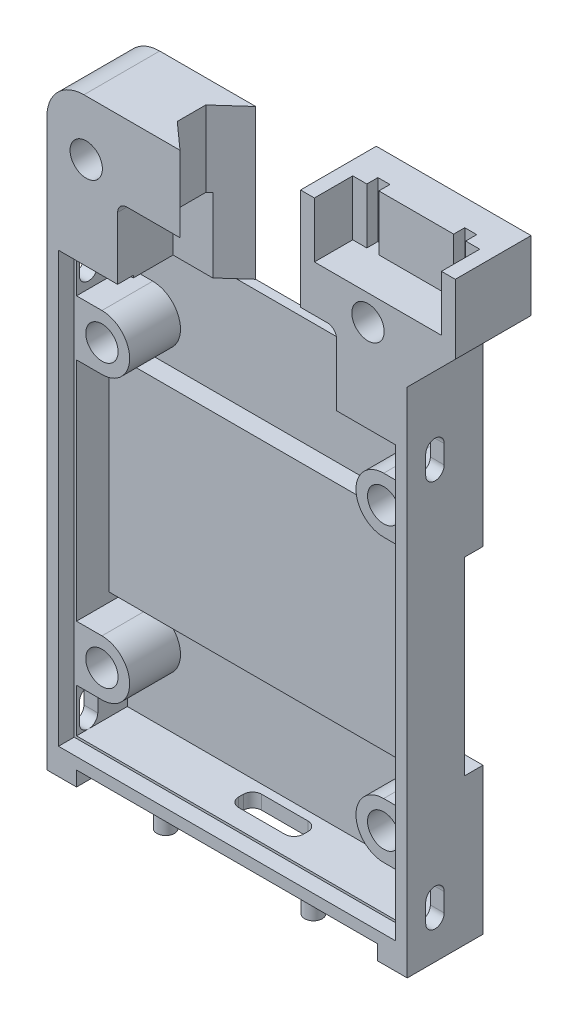
SolidWorks part; units mm, degrees
ref_plane "Front Plane" through (0, 0, 0) normal (0, 0, 1) x (1, 0, 0)
ref_plane "Top Plane" through (0, 0, 0) normal (0, 1, 0) x (1, 0, 0)
ref_plane "Right Plane" through (0, 0, 0) normal (1, 0, 0) x (0, 0, -1)
sketch "Sketch1" plane through (0, 0, 0) normal (0, 0, 1) x (1, 0, 0)
  line L0 (15.25, -20.35) -> (18, -20.35)
  line L1 (-19.5, -32.6) -> (19.5, -32.6)
  line L2 (-19.5, -32.6) -> (-19.5, 31.1)
  line L3 (-19.5, 31.1) -> (19.5, 31.1)
  line L4 (19.5, -32.6) -> (19.5, 31.1)
  line L5 (-15.25, -20.35) -> (-18, -20.35)
  line L6 (15.25, -26.35) -> (18, -26.35)
  line L7 (6.95, 31.1) -> (-15.5, 31.1) construction
  line L8 (-18, -31.1) -> (-18, 29.6)
  line L9 (-18, 29.6) -> (18, 29.6)
  line L10 (18, -31.1) -> (18, 29.6)
  line L11 (-18, -31.1) -> (18, -31.1)
  line L12 (-18, 14.9) -> (18, 14.9)
  line L13 (7.85, 14.9) -> (-4.95, 14.9) construction
  line L14 (-15.25, 4.15) -> (-18, 4.15)
  line L15 (-15.25, 10.15) -> (-18, 10.15)
  line L16 (15.25, 10.15) -> (18, 10.15)
  line L17 (15.25, 4.15) -> (18, 4.15)
  line L18 (-15.25, -26.35) -> (-18, -26.35)
  line L19 (19.5, -34.2) -> (19.5, -18.35) construction
  line L20 (-19.5, -34.2) -> (-19.5, -18.35) construction
  line L21 (15.3, -32.6) -> (-15.3, -32.6) construction
  line L22 (0, 31.1) -> (0, -32.6) construction
  line L23 (9.45, 26.9) -> (24.7, 26.9)
  line L24 (9.45, 26.9) -> (9.45, 33.9)
  line L25 (9.45, 33.9) -> (24.7, 33.9)
  line L26 (24.7, 26.9) -> (24.7, 33.9)
  line L27 (18, 29.6) -> (19.5, 31.1) construction
  line L28 (18.75, 30.35) -> (0, 30.35) construction
  line L29 (9.45, 26.9) -> (7.95, 26.9) construction
  line L30 (-7.95, 31.1) -> (7.95, 31.1)
  line L31 (-7.95, 31.1) -> (-7.95, 29.6)
  line L32 (-7.95, 29.6) -> (7.95, 29.6)
  line L33 (7.95, 31.1) -> (7.95, 29.6)
  line L34 (-7.95, 31.1) -> (7.95, 29.6) construction
  line L35 (-7.95, 29.6) -> (7.95, 31.1) construction
  line L36 (7.95, 26.9) -> (7.95, 29.6) construction
  line L37 (18, 29.6) -> (19.5, 29.6) construction
  line L38 (24.7, 26.4) -> (19.5, 21.2)
  line L39 (9.45, 33.9) -> (7.95, 33.9)
  line L40 (23.2, 33.9) -> (23.2, 26.9)
  line L41 (7.95, 33.9) -> (7.95, 31.1)
  line L42 (24.7, 30.4) -> (23.2, 30.4) construction
  line L43 (24.7, 26.9) -> (19.5, 26.9)
  line L44 (24.7, 26.9) -> (24.7, 26.4)
  line L45 (24.7, 26.4) -> (19.5, 26.4)
  line L46 (19.5, 26.9) -> (19.5, 26.4)
  circle A0 centre (15.25, -23.35) radius 1.75
  arc A1 (-15.5, 31.1) -> (-19.5, 27.1) centre (-15.5, 27.1) ccw construction
  circle A2 centre (15.25, -23.35) radius 3
  arc A3 (-15.5, 31.1) -> (-19.5, 27.1) centre (-15.5, 27.1) ccw
  arc A4 (-15.5, 29.6) -> (-18, 27.1) centre (-15.5, 27.1) ccw
  circle A6 centre (-15.25, -23.35) radius 1.75
  circle A7 centre (-15.25, -23.35) radius 1.75
  circle A8 centre (-15.25, 7.15) radius 1.75
  circle A9 centre (15.25, 7.15) radius 1.75
  circle A10 centre (15.25, 25.15) radius 1.75
  circle A11 centre (-15.25, 25.15) radius 1.75
  circle A12 centre (-15.25, -23.35) radius 3
  circle A13 centre (-15.25, -23.35) radius 3
  circle A14 centre (15.25, 7.15) radius 3
  circle A15 centre (-15.25, 7.15) radius 3
  dimension "D2" = 1.5
  dimension "D4" = 6
  dimension "D3" = 3.5
  dimension "D5" = 13.75
  dimension "D6" = 15.9
  dimension "D7" = 7
  dimension "D8" = 45
  dimension "D9" = 0.5
  dimension "D1" = 1.5
extrude "Base shape" add sketch "Sketch1" along normal up to surface (8.2 mm away) contours A15 L8 L9 L31 L3 A3 L2 L1 L4 L23 L10 A14 A2 L11 A12 | A12 L8 L18 | A12 L8 A6 | L8 A12 | A12 L5 L8 | A15 L8 L14 | A15 L8 A8 | L8 A15 | A15 L15 L8 | L23 A10 L24 L9 A4 L8 L12 L10 A11 | A4 L9 L8 | L33 L3 L31 L9 | L3 L33 L9 L24 | L24 L9 L10 L23 L4 L3 | L24 L23 L10 L9 | A14 L10 L16 | L10 A14 A9 | A14 L17 L10 | L10 A14 | L10 A2 L6 | A2 L10 A0 | L0 A2 L10 | A2 L10 | L40 L25 L24 L3 L4 L23 | L25 L40 L23 L26 | L38 L45 L4 | L45 L44 L23 L4 | L39 L41 L3 L24 region at (16.8481, -20.9099, 0) region at (17.3601, -20.8437, 0) region at (18.7469, -8.1, 0) region at (17.3601, -25.8563, 0) region at (18.1004, -23.35, 0) region at (17.3601, 4.6437, 0) region at (16.8481, 4.7099, 0) region at (18.1004, 7.15, 0) region at (17.3601, 9.6563, 0) region at (-17.3601, -25.8563, 0) region at (-0.6044, 21.831, 0) region at (-18.1004, -23.35, 0) region at (-17.9169, -23.35, 0) region at (13.725, 28.25, 0) region at (15.3803, 29.9053, 0) region at (-17.3601, -20.8437, 0) region at (22.1, 26.65, 0) region at (17.77, 31.4935, 0) region at (-17.3601, 9.6563, 0) region at (-17.4416, 29.0416, 0) region at (8.7, 30.35, 0) region at (21.2333, 24.6667, 0) region at (23.95, 30.4, 0) region at (-16.8481, 9.5901, 0) region at (-18.1004, 7.15, 0) region at (-17.3601, 4.6437, 0) region at (0, 30.35, 0) region at (8.7, 32.5, 0)
sketch "Sketch3" plane through (19.5, 0, 0) normal (1, 0, 0) x (0, 0, -1)
  line L1 (0, -18.35) -> (-2, -18.35)
  line L2 (0, -18.35) -> (0, 2.15)
  line L3 (0, 2.15) -> (-2, 2.15)
  line L4 (-2, -18.35) -> (-2, 2.15)
  line L5 (0, -18.35) -> (2, -18.35) construction
  line L6 (0, 2.15) -> (2, 2.15) construction
  line L7 (0, -32.6) -> (0, 21.2) construction
  dimension "D1" = 2
extrude "Strap cut" cut sketch "Sketch3" against normal through all
sketch "Sketch4" plane through (0, 31.1, 0) normal (0, 1, 0) x (1, 0, 0)
  line L2 (7.95, 0) -> (-5.0998, 0)
  line L4 (-15.5, 0) -> (7.95, 0) construction
  line L5 (-15.5, -8.2) -> (7.95, -8.2) construction
  line L6 (7.95, -8.2) -> (-5.0998, -8.2)
  line L12 (7.95, -8.3) -> (7.95, 0.1)
  line L13 (7.95, 0.1) -> (-4.9883, 0.1)
  line L14 (-4.9883, 0.1) -> (-7.95, -2.5553)
  line L15 (-7.95, -2.5553) -> (-7.95, -5.6447)
  line L16 (-7.95, -5.6447) -> (-4.9883, -8.3)
  line L17 (-4.9883, -8.3) -> (7.95, -8.3)
  line L18 (7.95, -8.3) -> (7.95, 0.1)
  line L19 (7.95, 0.1) -> (-4.9883, 0.1)
  line L20 (-4.9883, 0.1) -> (-7.95, -2.5553)
  line L21 (-7.95, -2.5553) -> (-7.95, -5.6447)
  line L22 (-7.95, -5.6447) -> (-4.9883, -8.3)
  line L23 (-4.9883, -8.3) -> (7.95, -8.3)
  dimension "D1" = 0.1
extrude "XT60 cut" cut sketch "Sketch4" against normal up to next contours L21 L22 L18 L20 region at (0.4142, 31.1, 4.1)
sketch "Sketch5" plane through (19.5, 0, 0) normal (1, 0, 0) x (0, 0, -1)
  line L1 (-8.2, -32.6) -> (-8.2, 21.2) construction
  line L2 (-6.2, -31.1) -> (-4.2, -31.1)
  line L3 (-6.2, -31.1) -> (-6.2, -27.1)
  line L4 (-6.2, -27.1) -> (-4.2, -27.1)
  line L5 (-4.2, -31.1) -> (-4.2, -27.1)
  line L6 (-8.2, -31.1) -> (0, -31.1) construction
  line L7 (-8.2, 14.9) -> (0, 14.9) construction
  line L8 (-6.2, 14.9) -> (-4.2, 14.9)
  line L9 (-6.2, 14.9) -> (-6.2, 10.9)
  line L10 (-6.2, 10.9) -> (-4.2, 10.9)
  line L11 (-4.2, 14.9) -> (-4.2, 10.9)
  line L14 (-5.2, -27.1) -> (-5.2, -31.1) construction
  line L15 (-5.2, 14.9) -> (-5.2, 10.9) construction
  circle A0 centre (-5.2, -28.1) radius 1
  circle A1 centre (-5.2, -30.1) radius 1
  circle A2 centre (-5.2, 13.9) radius 1
  circle A3 centre (-5.2, 11.9) radius 1
  point P20 (-5.2, -29.1)
  point P31 (-5.2, 12.9)
  dimension "D3" = 4
  dimension "D1" = 2
  dimension "D2" = 2
extrude "Power wires cut" cut sketch "Sketch5" against normal through all contours A2 | A3 | A3 A2 L9 | A3 L11 A2 | A1 | A0 | A1 L5 A0 | A1 A0 L3 region at (19.5, -30.1, 5.2) region at (19.5, -29.1, 5.9766) region at (19.5, -29.1, 4.4234) region at (19.5, -28.1, 5.2) region at (19.5, 13.9, 5.2) region at (19.5, 12.9, 5.9766) region at (19.5, 12.9, 4.4234) region at (19.5, 11.9, 5.2)
sketch "Sketch6" plane through (0, 0, 8.2) normal (0, 0, 1) x (1, 0, 0)
  line L0 (-7.85, 15.9) -> (-7.85, 21.9) construction
  line L1 (-8.85, 22.9) -> (-10.85, 22.9) construction
  line L2 (-11.85, 15.9) -> (-11.85, 21.9) construction
  line L3 (-8.85, 14.9) -> (-10.85, 14.9) construction
  line L4 (-7.85, 15.9) -> (-7.85, 21.9)
  line L5 (-8.85, 22.9) -> (-10.85, 22.9)
  line L6 (-11.85, 15.9) -> (-11.85, 21.9)
  line L7 (-8.85, 14.9) -> (-10.85, 14.9)
  line L8 (7.85, 15.9) -> (7.85, 21.9) construction
  line L9 (8.85, 22.9) -> (10.85, 22.9) construction
  line L10 (11.85, 15.9) -> (11.85, 21.9) construction
  line L11 (8.85, 14.9) -> (10.85, 14.9) construction
  line L12 (7.85, 15.9) -> (7.85, 21.9)
  line L13 (8.85, 22.9) -> (10.85, 22.9)
  line L14 (11.85, 15.9) -> (11.85, 21.9)
  line L15 (8.85, 14.9) -> (10.85, 14.9)
  line L17 (-11.85, 15.9) -> (-7.85, 15.9)
  line L18 (-11.85, 15.9) -> (-11.85, 14.9)
  line L19 (-11.85, 14.9) -> (-7.85, 14.9)
  line L20 (-7.85, 15.9) -> (-7.85, 14.9)
  line L22 (11.85, 15.9) -> (7.85, 15.9)
  line L23 (11.85, 15.9) -> (11.85, 14.9)
  line L24 (11.85, 14.9) -> (7.85, 14.9)
  line L25 (7.85, 15.9) -> (7.85, 14.9)
  line L26 (-18, 14.9) -> (-5.0998, 14.9) construction
  line L27 (11.85, 21.9) -> (7.85, 21.9)
  line L28 (11.85, 21.9) -> (11.85, 22.9)
  line L29 (11.85, 22.9) -> (7.85, 22.9)
  line L30 (7.85, 21.9) -> (7.85, 22.9)
  line L31 (-8.85, 22.9) -> (7.95, 22.9)
  line L32 (-8.85, 22.9) -> (-8.85, 14.9)
  line L33 (-8.85, 14.9) -> (7.95, 14.9)
  line L34 (7.95, 22.9) -> (7.95, 14.9)
  line L35 (7.95, 14.9) -> (18, 14.9) construction
  line L36 (7.95, 14.9) -> (7.95, 33.9) construction
  arc A0 (-8.85, 14.9) -> (-7.85, 15.9) centre (-8.85, 15.9) ccw construction
  arc A1 (-7.85, 21.9) -> (-8.85, 22.9) centre (-8.85, 21.9) ccw construction
  arc A2 (-10.85, 22.9) -> (-11.85, 21.9) centre (-10.85, 21.9) ccw construction
  arc A3 (-11.85, 15.9) -> (-10.85, 14.9) centre (-10.85, 15.9) ccw construction
  arc A4 (-8.85, 14.9) -> (-7.85, 15.9) centre (-8.85, 15.9) ccw
  arc A5 (-7.85, 21.9) -> (-8.85, 22.9) centre (-8.85, 21.9) ccw
  arc A6 (-10.85, 22.9) -> (-11.85, 21.9) centre (-10.85, 21.9) ccw
  arc A7 (-11.85, 15.9) -> (-10.85, 14.9) centre (-10.85, 15.9) ccw
  arc A8 (8.85, 22.9) -> (7.85, 21.9) centre (8.85, 21.9) ccw construction
  arc A9 (11.85, 21.9) -> (10.85, 22.9) centre (10.85, 21.9) ccw construction
  arc A10 (10.85, 14.9) -> (11.85, 15.9) centre (10.85, 15.9) ccw construction
  arc A11 (7.85, 15.9) -> (8.85, 14.9) centre (8.85, 15.9) ccw construction
  arc A12 (8.85, 22.9) -> (7.85, 21.9) centre (8.85, 21.9) ccw
  arc A13 (11.85, 21.9) -> (10.85, 22.9) centre (10.85, 21.9) ccw
  arc A14 (10.85, 14.9) -> (11.85, 15.9) centre (10.85, 15.9) ccw
  arc A15 (7.85, 15.9) -> (8.85, 14.9) centre (8.85, 15.9) ccw
  line M1 (7.95, 33.9) -> (7.95, 14.9)
  line M15 (-5.0998, 14.9) -> (-5.0998, 31.1)
extrude "IO wires cut" cut sketch "Sketch6" against normal blind 6 contours L33 L25 L12 L30 L31 M15 | A5 L4 L20 L31 M15 | L4 A5 L32 L17 | L5 A6 L6 L17 L32 | A7 L18 | L17 A7 L32 | L32 A4 L17 | A4 L20 | A12 L29 L30 M1 | L27 L12 L22 M1 | L22 A15 M1 | A15 L25 L24 L34 | A15 L34 | A15 A14 L22 M1 | A14 L23 | L14 L27 L22 M1 | L27 A13 L13 A12 L34 | A12 L29 M1 region at (-8.3587, 19.2964, 8.2) region at (-8.4256, 15.4756, 8.2) region at (-6.4903, 18.9365, 8.2) region at (-8.0734, 15.1234, 8.2) region at (-10.2516, 15.4213, 8.2) region at (-10.3368, 19.3662, 8.2) region at (-11.6266, 15.1234, 8.2) region at (1.3751, 18.9, 8.2) region at (7.8959, 15.2606, 8.2) region at (7.8959, 22.5394, 8.2) region at (8.1604, 15.056, 8.2) region at (7.9, 18.9, 8.2) region at (7.9098, 15.7354, 8.2) region at (8.1604, 22.744, 8.2) region at (9.8661, 15.4307, 8.2) region at (9.9, 18.9, 8.2) region at (9.8661, 22.3693, 8.2) region at (11.6266, 15.1234, 8.2)
sketch "Sketch7" plane through (-18, 0, 0) normal (1, 0, 0) x (0, 0, -1)
  line L6 (0, -18.35) -> (0, -20.35)
  line L7 (-2, -18.35) -> (0, -18.35)
  line L8 (-2, 2.15) -> (-2, -18.35)
  line L9 (0, 2.15) -> (-2, 2.15)
  line L12 (0, 3.15) -> (-3, 3.15)
  line L13 (-3, 3.15) -> (-3, -19.35)
  line L14 (-3, -19.35) -> (-1, -19.35)
  line L15 (-1, -19.35) -> (-1, -20.35)
  line L16 (-1, -20.35) -> (0, -20.35)
  line L17 (0, 3.15) -> (-1, 3.15)
  line L19 (0, -31.1) -> (-1, -31.1)
  line L22 (0, -31.1) -> (0, -20.35)
  line L23 (0, -20.35) -> (-1, -20.35)
  line L24 (-1, -31.1) -> (-1, -20.35)
  line L25 (0, 3.15) -> (0, 14.9)
  line L26 (0, 14.9) -> (-1, 14.9)
  line L27 (-1, 3.15) -> (-1, 14.9)
  line L28 (-5.2, 14.9) -> (0, 14.9) construction
  line L31 (0, -20.35) -> (0, -18.35) construction
  line L32 (0, 2.15) -> (-2, 2.15) construction
  line M48 (0, -20.35) -> (0, -18.35)
  line M49 (0, -18.35) -> (-2, -18.35)
  line M50 (-2, -18.35) -> (-2, 2.15)
  line M51 (-2, 2.15) -> (0, 2.15)
  line M52 (0, 2.15) -> (0, 4.15)
  line M53 (0, 4.15) -> (-8.2, 4.15)
  line M55 (-8.2, -20.35) -> (0, -20.35)
  dimension "D1" = 1
extrude "Bottom" add sketch "Sketch7" along normal up to surface (36 mm away) contours L27 L25 L26 M53 | L27 L12 M52 M53 | L14 L15 L12 L13 M55 M48 M49 M50 M51 M52 | L24 L19 L22 M55 region at (-18, -8.5273, 2.2091) region at (-18, -25.725, 0.5) region at (-18, 3.65, 0.5) region at (-18, 9.525, 0.5) up to face at (18, -8.1, 2.55)
sketch "Sketch9" plane through (0, 0, 0) normal (0, 0, -1) x (-1, 0, 0)
  circle A0 centre (15.25, -23.35) radius 1.75 construction
  circle A1 centre (-15.25, 7.15) radius 1.75 construction
  circle A2 centre (15.25, 7.15) radius 1.75 construction
  circle A3 centre (15.25, -23.35) radius 1.75 construction
  circle A4 centre (15.25, -23.35) radius 1.75
  circle A5 centre (-15.25, 7.15) radius 1.75
  circle A6 centre (15.25, 7.15) radius 1.75
  circle A7 centre (15.25, -23.35) radius 1.75
  circle A8 centre (-15.25, -23.35) radius 1.75 construction
  circle A9 centre (-15.25, -23.35) radius 1.75
extrude "Bottom holes" cut sketch "Sketch9" against normal up to next contours A5 | A6 | A4 | A9 region at (-15.25, -23.35, 0) region at (15.25, 7.15, 0) region at (-15.25, 7.15, 0) region at (15.25, -23.35, 0)
sketch "Sketch8" plane through (0, 0, 8.2) normal (0, 0, 1) x (1, 0, 0)
  line L0 (-6.2152, 14.9) -> (-18, 14.9) construction
  line L1 (-18.25, 15.15) -> (18.25, 15.15)
  line L2 (-18.25, 15.15) -> (-18.25, -31.35)
  line L3 (-18.25, -31.35) -> (18.25, -31.35)
  line L4 (18.25, 15.15) -> (18.25, -31.35)
  line L5 (-18, 14.9) -> (-18.25, 14.9) construction
  line L6 (-18, 14.9) -> (-18, 15.15) construction
  line L7 (18, 14.9) -> (18.25, 14.9) construction
  line L8 (-18, -31.1) -> (-18, -31.35) construction
  dimension "D1" = 0.25
extrude "PCB cut" cut sketch "Sketch8" against normal blind 1.7
sketch "Sketch11" plane through (0, -32.6, 0) normal (0, -1, 0) x (1, 0, 0)
  line L0 (19.5, 8.2) -> (19.5, 0) construction
  line L1 (-19.5, 8.2) -> (19.5, 8.2)
  line L2 (-19.5, 8.2) -> (-19.5, -1.8)
  line L3 (-19.5, -1.8) -> (19.5, -1.8)
  line L4 (19.5, 8.2) -> (19.5, -1.8)
  line L5 (-19.5, 3.2) -> (19.5, 3.2) construction
  line L6 (0, -1.8) -> (0, 8.2) construction
  line L8 (-2.5, 4.45) -> (2.5, 4.45)
  line L9 (-3.5, 3.45) -> (-3.5, 2.95)
  line L10 (-2.5, 1.95) -> (2.5, 1.95)
  line L11 (3.5, 3.45) -> (3.5, 2.95)
  line L12 (-3.5, 4.45) -> (3.5, 1.95) construction
  line L13 (-3.5, 1.95) -> (3.5, 4.45) construction
  arc A0 (2.5, 4.45) -> (3.5, 3.45) centre (2.5, 3.45) cw
  arc A1 (2.5, 1.95) -> (3.5, 2.95) centre (2.5, 2.95) ccw
  arc A2 (-3.5, 2.95) -> (-2.5, 1.95) centre (-2.5, 2.95) ccw
  arc A3 (-2.5, 4.45) -> (-3.5, 3.45) centre (-2.5, 3.45) ccw
  point P11 (0, 3.2)
  dimension "D4" = 1
  dimension "D1" = 10
  dimension "D2" = 7
  dimension "D3" = 2.5
extrude "Ledbar wires cut" cut sketch "Sketch11" against normal up to next contours L8 A3 L9 A2 L10 A1 L11 A0 region at (0, -32.6, 3.2)
sketch "Sketch13" plane through (0, -32.6, 0) normal (0, -1, 0) x (1, 0, 0)
  line L0 (-19.5, 8.2) -> (19.5, 8.2) construction
  line L1 (19.5, 0) -> (16.3, 0)
  line L2 (19.5, 0) -> (19.5, 8.2)
  line L3 (19.5, 8.2) -> (16.3, 8.2)
  line L4 (16.3, 0) -> (16.3, 8.2)
  line L5 (16.1, -1.8) -> (16.1, 8.2) construction
  line L6 (0, 8.2) -> (0, 0) construction
  line L7 (-19.5, 0) -> (-16.3, 0)
  line L8 (-19.5, 0) -> (-19.5, 8.2)
  line L9 (-19.5, 8.2) -> (-16.3, 8.2)
  line L10 (-16.3, 0) -> (-16.3, 8.2)
  dimension "D1" = 0.2
extrude "Ledbar sides" add sketch "Sketch13" along normal blind 1.6
sketch "Sketch14" plane through (0, -32.6, 0) normal (0, -1, 0) x (1, 0, 0)
  circle A0 centre (8, 6.85) radius 0.95
  circle A1 centre (-8, 6.85) radius 0.95
  dimension "D1" = 1.9
extrude "Ledbar mounts" add sketch "Sketch14" along normal blind 2
sketch "Sketch16" plane through (0, 33.9, 0) normal (0, 1, 0) x (1, 0, 0)
  line L0 (7.95, -6.125) -> (24.7, -6.125) construction
  line L1 (7.95, -8.2) -> (24.7, -8.2) construction
  line L2 (21.675, -2.85) -> (20.375, -2.85)
  line L3 (20.375, -4.05) -> (20.375, -2.85)
  line L4 (9.45, -4.05) -> (23.2, -4.05)
  line L5 (9.45, -4.05) -> (9.45, -8.2)
  line L6 (9.45, -8.2) -> (23.2, -8.2)
  line L7 (23.2, -4.05) -> (23.2, -8.2)
  line L8 (9.45, -4.05) -> (23.2, -8.2) construction
  line L9 (9.45, -8.2) -> (23.2, -4.05) construction
  line L10 (24.7, -8.2) -> (24.7, 0) construction
  line L11 (7.95, -8.2) -> (7.95, 0) construction
  line L12 (16.325, -8.2) -> (16.325, -4.05) construction
  line L13 (11.625, -2.85) -> (11.625, -4.05) construction
  line L14 (10.975, -4.05) -> (12.275, -4.05)
  line L15 (10.975, -4.05) -> (10.975, -2.85)
  line L16 (10.975, -2.85) -> (12.275, -2.85)
  line L17 (12.275, -4.05) -> (12.275, -2.85)
  line L18 (10.975, -2.85) -> (10.975, -8.2) construction
  line L19 (21.675, -4.05) -> (21.675, -2.85)
  point P6 (16.325, -6.125)
  dimension "D1" = 13.75
  dimension "D2" = 4.15
  dimension "D3" = 1.3
  dimension "D4" = 1.2
  dimension "D5" = 4.7
extrude "Balance plug cut" cut sketch "Sketch16" against normal blind 6 contours L7 L4 L5 L6 | L4 L17 L16 L15 | L4 L19 L2 L3 region at (21.025, 33.9, 3.45) region at (16.325, 33.9, 6.125) region at (11.625, 33.9, 3.45)
sketch "Sketch10" [suppressed] plane through (0, 0, 2) normal (0, 0, -1) x (-1, 0, 0)
  line L0 (0, 2.15) -> (0, -18.35) construction
  line L1 (19.5, 2.15) -> (-19.5, 2.15) construction
  line L2 (19.5, -18.35) -> (-19.5, -18.35) construction
  line L3 (19.5, 2.15) -> (19.5, -18.35) construction
  line L4 (-19.5, 1.15) -> (19.5, 1.15)
  line L5 (-19.5, 1.15) -> (-19.5, 0.65)
  line L6 (-19.5, 0.65) -> (19.5, 0.65)
  line L7 (19.5, 1.15) -> (19.5, 0.65)
  line L8 (-19.5, 1.15) -> (19.5, 0.65) construction
  line L9 (-19.5, 0.65) -> (19.5, 1.15) construction
  line L10 (-19.5, 2.15) -> (19.5, 2.15) construction
  line L11 (-19.5, -1.35) -> (19.5, -1.35)
  line L12 (19.5, -0.85) -> (19.5, -1.35)
  line L13 (-19.5, -0.85) -> (19.5, -0.85)
  line L14 (-19.5, -0.85) -> (-19.5, -1.35)
  line L15 (-19.5, -3.35) -> (19.5, -3.35)
  line L16 (19.5, -2.85) -> (19.5, -3.35)
  line L17 (-19.5, -2.85) -> (19.5, -2.85)
  line L18 (-19.5, -2.85) -> (-19.5, -3.35)
  line L19 (-19.5, -5.35) -> (19.5, -5.35)
  line L20 (19.5, -4.85) -> (19.5, -5.35)
  line L21 (-19.5, -4.85) -> (19.5, -4.85)
  line L22 (-19.5, -4.85) -> (-19.5, -5.35)
  line L23 (-19.5, -7.35) -> (19.5, -7.35)
  line L24 (19.5, -6.85) -> (19.5, -7.35)
  line L25 (-19.5, -6.85) -> (19.5, -6.85)
  line L26 (-19.5, -6.85) -> (-19.5, -7.35)
  line L27 (-19.5, -9.35) -> (19.5, -9.35)
  line L28 (19.5, -8.85) -> (19.5, -9.35)
  line L29 (-19.5, -8.85) -> (19.5, -8.85)
  line L30 (-19.5, -8.85) -> (-19.5, -9.35)
  line L31 (-19.5, -11.35) -> (19.5, -11.35)
  line L32 (19.5, -10.85) -> (19.5, -11.35)
  line L33 (-19.5, -10.85) -> (19.5, -10.85)
  line L34 (-19.5, -10.85) -> (-19.5, -11.35)
  line L35 (-19.5, -13.35) -> (19.5, -13.35)
  line L36 (19.5, -12.85) -> (19.5, -13.35)
  line L37 (-19.5, -12.85) -> (19.5, -12.85)
  line L38 (-19.5, -12.85) -> (-19.5, -13.35)
  line L39 (-19.5, -15.35) -> (19.5, -15.35)
  line L40 (19.5, -14.85) -> (19.5, -15.35)
  line L41 (-19.5, -14.85) -> (19.5, -14.85)
  line L42 (-19.5, -14.85) -> (-19.5, -15.35)
  line L43 (-19.5, -17.35) -> (19.5, -17.35)
  line L44 (19.5, -16.85) -> (19.5, -17.35)
  line L45 (-19.5, -16.85) -> (19.5, -16.85)
  line L46 (-19.5, -16.85) -> (-19.5, -17.35)
  point P6 (0, 0.9)
  dimension "D1" = 1
  dimension "D2" = 0.5
  dimension "D4" = 2
  dimension "D3" = 10
extrude "3D print ribs" [suppressed] add sketch "Sketch10" along normal up to surface (2 mm away) up to face at (-17, 7.15, 0)
sketch "Sketch15" [suppressed] plane through (0, 0, 0) normal (0, 0, -1) x (-1, 0, 0)
  line L0 (-8, -34.6) -> (-8, -32.6) construction
  line L1 (-8.95, -34.6) -> (-7.05, -34.6) construction
  line L2 (-8.95, -32.6) -> (-7.05, -32.6) construction
  line L3 (0, -32.6) -> (0, 14.9) construction
  line L4 (-8.25, -34.6) -> (-7.75, -34.6)
  line L5 (-8.25, -34.6) -> (-8.25, -32.6)
  line L6 (-8.25, -32.6) -> (-7.75, -32.6)
  line L7 (-7.75, -34.6) -> (-7.75, -32.6)
  line L8 (-8.25, -34.6) -> (-7.75, -32.6) construction
  line L9 (-8.25, -32.6) -> (-7.75, -34.6) construction
  line L10 (16.3, -32.6) -> (-16.3, -32.6) construction
  line L11 (-7.95, 14.9) -> (5.0998, 14.9) construction
  line L12 (8.25, -32.6) -> (7.75, -32.6)
  line L13 (7.75, -34.6) -> (7.75, -32.6)
  line L14 (8.25, -34.6) -> (7.75, -34.6)
  line L15 (8.25, -34.6) -> (8.25, -32.6)
  point P6 (-8, -33.6)
  dimension "D1" = 0.5
extrude "3D print led supports" [suppressed] add sketch "Sketch15" against normal up to next
